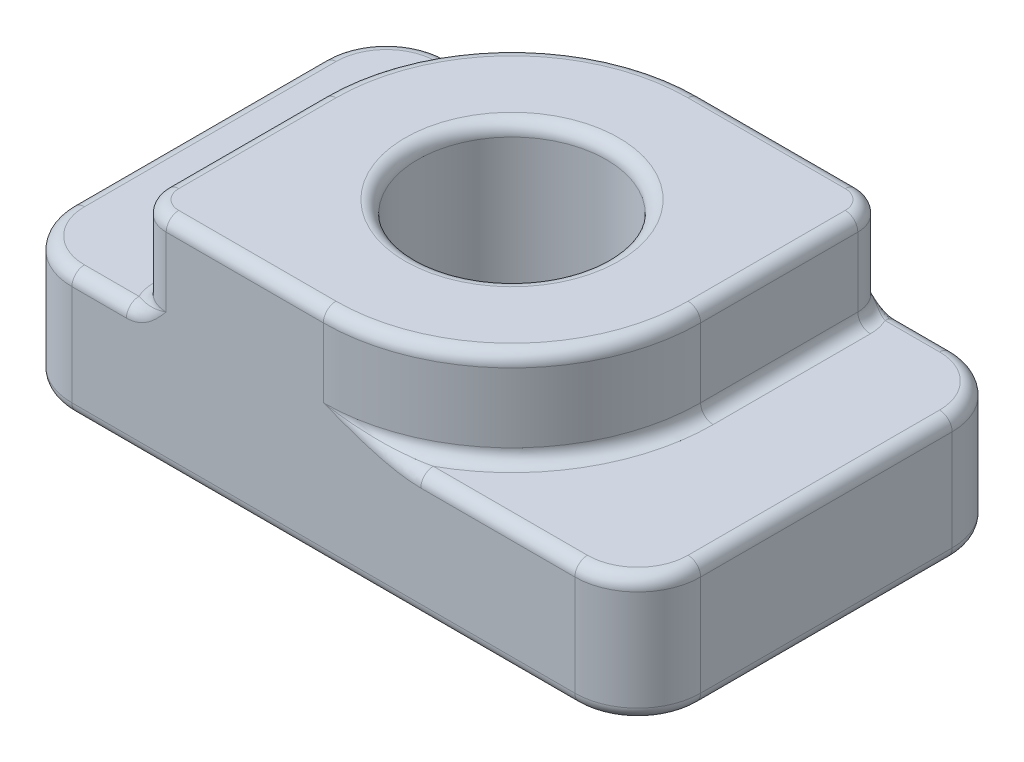
SolidWorks part; units mm, degrees
material "Galvanized Steel"
ref_plane "Plano frontal" through (0, 0, 0) normal (0, 0, 1) x (1, 0, 0)
ref_plane "Plano superior" through (0, 0, 0) normal (0, 1, 0) x (1, 0, 0)
ref_plane "Plano direito" through (0, 0, 0) normal (1, 0, 0) x (0, 0, -1)
sketch "Esboço1" plane through (0, 0, 0) normal (0, 1, 0) x (1, 0, 0)
  line L1 (-5, 3) -> (5, 3)
  line L2 (-5, 3) -> (-5, -3)
  line L3 (-5, -3) -> (5, -3)
  line L4 (5, 3) -> (5, -3)
  line L5 (-5, 3) -> (5, -3) construction
  line L6 (-5, -3) -> (5, 3) construction
  circle A0 centre (0, 0) radius 1.5
  point P0 (0, 0)
  dimension "D1" = 3
  dimension "D2" = 10
  dimension "D3" = 6
extrude "Ressalto-extrusão1" add sketch "Esboço1" along normal blind 2
sketch "Esboço2" plane through (0, 2, 0) normal (0, 1, 0) x (1, 0, 0)
  line L0 (-5, -3) -> (5, -3) construction
  line L3 (0, 3) -> (2.5, 3)
  line L4 (-3, 0) -> (-3, -2.5)
  line L5 (-2.5, -3) -> (0, -3)
  line L6 (3, 2.5) -> (3, 0)
  line L7 (-3, 3) -> (3, -3) construction
  line L8 (-3, -3) -> (3, 3) construction
  arc A0 (0, -3) -> (3, 0) centre (0, 0) ccw
  arc A1 (0, 3) -> (-3, 0) centre (0, 0) ccw
  arc A2 (2.5, 3) -> (3, 2.5) centre (2.5, 2.5) cw
  arc A3 (-3, -2.5) -> (-2.5, -3) centre (-2.5, -2.5) ccw
  point P0 (0, 0)
  dimension "D2" = 3
  dimension "D3" = 0.5
  dimension "D1" = 6
extrude "Ressalto-extrusão2" add sketch "Esboço2" along normal blind 1.5
sketch "Esboço3" plane through (0, 2, 0) normal (0, -1, 0) x (1, 0, 0)
  circle A0 centre (0, 0) radius 1.5
  dimension "D1" = 3
extrude "Corte-extrusão1" cut sketch "Esboço3" against normal blind 1.5
fillet "Filete1" radius 1 4 edges at (5, 1, 3) (5, 1, -3) (-5, 1, -3) (-5, 1, 3)
fillet "Filete2" radius 0.2 34 edges at (2.1213, 2, 2.1213) (3, 2, -1.25) (2.8536, 2, -2.8536) (3.25, 2, -3) (4.7071, 2, -2.7071) (5, 2, 0) (4.7071, 2, 2.7071) (2, 2, 3) (0, 0, 1.5) (4.7071, 0, -2.7071) (0, 0, -3) (-4.7071, 0, -2.7071) (-5, 0, 0) (-4.7071, 0, 2.7071) (0, 0, 3) (4.7071, 0, 2.7071) (5, 0, 0) (-2.1213, 2, -2.1213) (-3, 2, 1.25) (-2.8536, 2, 2.8536) (-3.25, 2, 3) (-4.7071, 2, 2.7071) (-5, 2, 0) (-4.7071, 2, -2.7071) (-2, 2, -3) (-1.25, 3.5, 3) (-2.8536, 3.5, 2.8536) (-3, 3.5, 1.25) (-2.1213, 3.5, -2.1213) (1.25, 3.5, -3) (2.8536, 3.5, -2.8536) (3, 3.5, -1.25) (2.1213, 3.5, 2.1213) (0, 3.5, -1.5)
